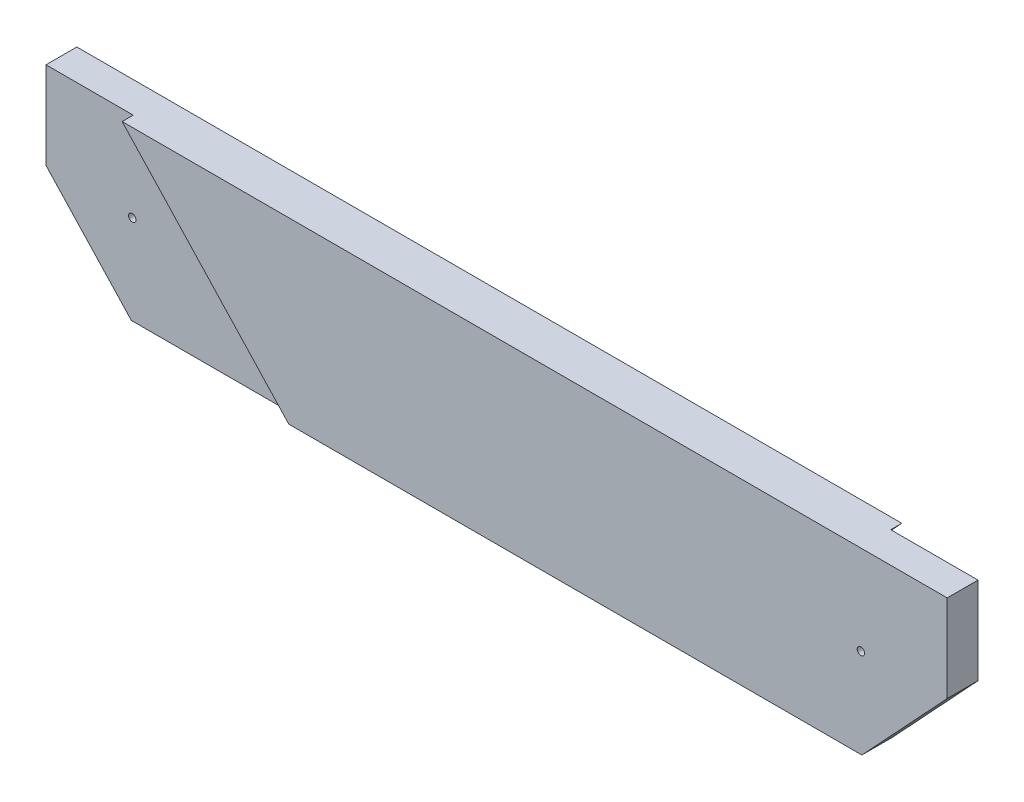
SolidWorks part; units mm, degrees
material "Pine"
ref_plane "Front Plane" through (0, 0, 0) normal (0, 0, 1) x (1, 0, 0)
ref_plane "Top Plane" through (0, 0, 0) normal (0, 1, 0) x (1, 0, 0)
ref_plane "Right Plane" through (0, 0, 0) normal (1, 0, 0) x (0, 0, -1)
sketch "Sketch1" plane through (0, 0, 0) normal (0, 0, 1) x (1, 0, 0)
  line L1 (-370, 72.5) -> (370, 72.5)
  line L2 (-370, 72.5) -> (-370, -72.5)
  line L3 (-370, -72.5) -> (370, -72.5)
  line L4 (370, 72.5) -> (370, -72.5)
  line L5 (-370, 72.5) -> (370, -72.5) construction
  line L6 (-370, -72.5) -> (370, 72.5) construction
  point P0 (0, 0)
  dimension "D1" = 740
  dimension "D2" = 145
extrude "Boss-Extrude1" add sketch "Sketch1" along normal blind 34
ref_axis "Axis1" through (-370, 0, 34) along (1, 0, 0)
sketch "Sketch2" plane through (0, 0, 34) normal (0, 0, 1) x (1, 0, 0)
  line L2 (0, -18.7) -> (0, 18.7) construction
  circle A0 centre (-300, 0) radius 3
  dimension "D1" = 300
extrude "Cut-Extrude1" cut sketch "Sketch2" against normal through all
mirror "Mirror1" about plane through (0, 0, 0) normal (1, 0, 0) of "Cut-Extrude1"
sketch "Sketch3" plane through (0, 0, 0) normal (0, 0, -1) x (-1, 0, 0)
  line L0 (-370, 1.7696) -> (-300.7767, -72.5)
  line L1 (-370, 72.5) -> (-370, -72.5) construction
  line L2 (370, -72.5) -> (-370, -72.5) construction
  line L3 (-300.7767, -72.5) -> (-300.7767, -90.032)
  line L4 (-300.7767, -90.032) -> (-434.7285, -90.032)
  line L5 (-434.7285, -90.032) -> (-434.7285, 1.7696)
  line L6 (-434.7285, 1.7696) -> (-370, 1.7696)
  line L7 (300.7767, -72.5) -> (370, 1.7696)
  line L8 (370, 72.5) -> (370, -72.5) construction
  line L9 (370, 1.7696) -> (452.6155, -36.8038)
  line L10 (452.6155, -36.8038) -> (398.5933, -163.6704)
  line L11 (398.5933, -163.6704) -> (300.7767, -72.5)
  line L12 (370, 1.7696) -> (-263.1164, -677.5) construction
  line L13 (338.4239, -758.2974) -> (-411.5761, 46.3765) construction
extrude "Cut-Extrude2" cut sketch "Sketch3" against normal through all
sketch "Sketch4" plane through (0, 0, 34) normal (0, 0, 1) x (1, 0, 0)
  line L0 (-485.7146, 114.0442) -> (-337.9448, 114.0442)
  line L1 (-337.9448, 114.0442) -> (-115.1982, -124.9402)
  line L2 (-115.1982, -124.9402) -> (-485.7146, -111.9101)
  line L3 (-485.7146, -111.9101) -> (-485.7146, 114.0442)
  line L4 (383.1164, -659.5811) -> (-299.2233, 72.5) construction
extrude "Cut-Extrude3" cut sketch "Sketch4" against normal blind 9
sketch "Sketch5" plane through (0, 0, 0) normal (0, 0, -1) x (-1, 0, 0)
  line L0 (-568.7059, 127.3531) -> (-361.8332, 139.6741)
  line L1 (-361.8332, 139.6741) -> (-111.6961, -128.6976)
  line L2 (-111.6961, -128.6976) -> (-536.327, -147.1062)
  line L3 (-536.327, -147.1062) -> (-568.7059, 127.3531)
  line L4 (411.5761, -690.1156) -> (-338.4239, 114.5583) construction
extrude "Cut-Extrude4" cut sketch "Sketch5" against normal blind 9
